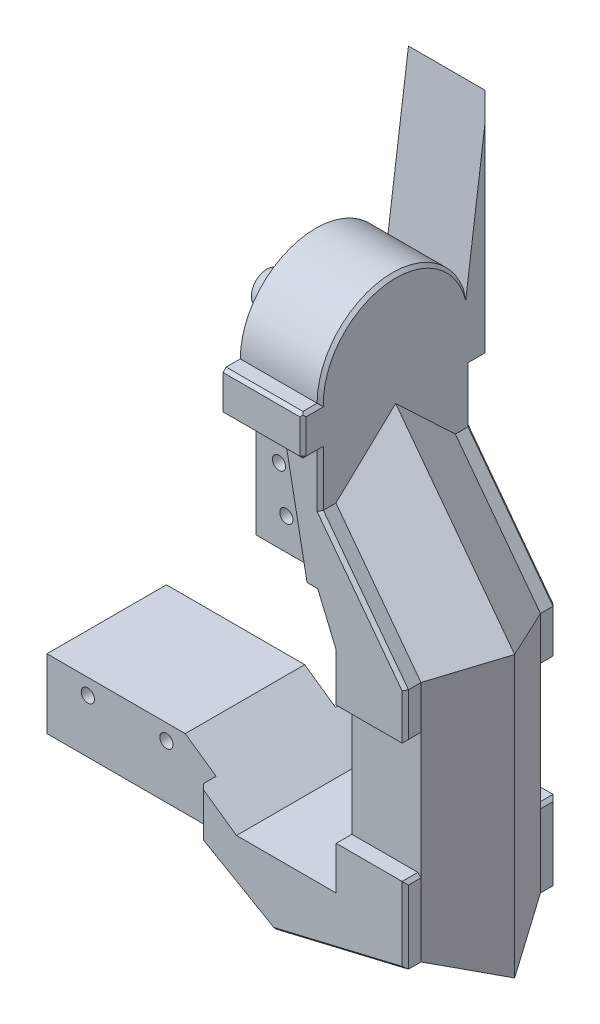
SolidWorks part; units mm, degrees
ref_plane "前视基准面" through (0, 0, 0) normal (0, 0, 1) x (1, 0, 0)
ref_plane "上视基准面" through (0, 0, 0) normal (0, 1, 0) x (1, 0, 0)
ref_plane "右视基准面" through (0, 0, 0) normal (1, 0, 0) x (0, 0, -1)
other "Configuration Table"
sketch "草图1" plane through (0, 0, 0) normal (0, 0, 1) x (1, 0, 0)
  line L0 (0, 0) -> (53.8, 0)
  line L1 (53.8, 0) -> (77, -13.3945)
  line L2 (77, -13.3945) -> (119, -3.4144)
  line L3 (119, -3.4144) -> (119, 73.5856)
  line L4 (119, 73.5856) -> (91.9365, 109.5)
  line L5 (91.9365, 109.5) -> (91.9365, 158)
  line L6 (91.9365, 158) -> (66.5044, 158)
  line L7 (66.5044, 158) -> (66.5044, 88)
  line L8 (66.5044, 88) -> (91.1544, 88)
  line L9 (91.1544, 88) -> (97, 74.0856)
  line L12 (65.3, 7.0856) -> (44, 22)
  line L13 (44, 22) -> (0, 22)
  line L14 (0, 22) -> (0, 0)
  line L15 (65.3, 7.0856) -> (97, 7.0856)
  line L16 (97, 7.0856) -> (97, 74.0856)
  circle A0 centre (73.8244, 111.53) radius 2.1
  circle A1 centre (76.1544, 98.03) radius 2.1
  circle A2 centre (13, 17) radius 2.1
  circle A3 centre (38, 17) radius 2.1
  dimension "D21" = 4.2
  dimension "D24" = 4.2
  dimension "D29" = 4.2
  dimension "D30" = 4.2
  dimension "D1" = 44
  dimension "D2" = 53
  dimension "D3" = 22
  dimension "D4" = 145
  dimension "D5" = 150
  dimension "D6" = 31.7
  dimension "D7" = 22
  dimension "D8" = 23.2
  dimension "D9" = 42
  dimension "D10" = 10.5
  dimension "D11" = 24.65
  dimension "D12" = 66
  dimension "D13" = 67.212
  dimension "D14" = 77
  dimension "D15" = 67
  dimension "D16" = 70
  dimension "D17" = 48.5
  dimension "D18" = 143
  dimension "D19" = 7.32
  dimension "D20" = 23.53
  dimension "D22" = 9.65
  dimension "D23" = 10.03
  dimension "D25" = 13
  dimension "D26" = 38
  dimension "D27" = 17
  dimension "D28" = 17
extrude "凸台-拉伸1" add sketch "草图1" along normal blind 38
sketch "草图2" plane through (91.9365, 0, 0) normal (1, 0, 0) x (0, 0, -1)
  line L0 (-38, 109.5) -> (-38, 158) construction
  line L1 (-38, 158) -> (0, 158) construction
  line L2 (0, 109.5) -> (0, 158) construction
  line L3 (-19, 109.5) -> (-19, 164.3174) construction
  line L5 (-38, 139) -> (-38, 158)
  line L6 (-38, 158) -> (0, 158)
  line L7 (0, 158) -> (0, 139)
  arc A0 (-38, 139) -> (0, 139) centre (-19, 139) cw
  circle A1 centre (-19, 139) radius 3
  line M6 (0, 109.5) -> (0, 158)
  line M7 (0, 158) -> (-38, 158)
  line M8 (-38, 158) -> (-38, 109.5)
  dimension "D1" = 6
extrude "切除-拉伸1" cut sketch "草图2" against normal through all contours A0 L6 M8 | A0 M7 M6
sketch "草图3" plane through (66.5044, 0, 0) normal (-1, 0, 0) x (0, 0, 1)
  line L3 (0, 139) -> (0, 88)
  line L4 (0, 88) -> (38, 88)
  line L5 (38, 88) -> (38, 139)
  line L6 (0, 139) -> (0, 88)
  line L7 (0, 88) -> (38, 88)
  line L8 (38, 88) -> (38, 139)
  circle A0 centre (19, 139) radius 3.15
  arc A1 (38, 139) -> (0, 139) centre (19, 139) ccw
  arc A2 (38, 139) -> (0, 139) centre (19, 139) ccw
  dimension "D2" = 6.3
  dimension "D1" = 0
extrude "切除-拉伸3" cut sketch "草图3" against normal blind 1 contours A0
ref_plane "基准面1" through (77, 0, 0) normal (-1, 0, 0) x (0, 0, 1)
sketch "草图4" plane through (77, 0, 0) normal (-1, 0, 0) x (0, 0, 1)
  line L0 (38, -13.3945) -> (0, -13.3945) construction
  line L1 (38, -13.3945) -> (0, -13.3945)
  line L2 (0, -13.3945) -> (19, -24.4851)
  line L3 (19, -24.4851) -> (38, -13.3945)
  dimension "D1" = 22
ref_plane "基准面2" through (0, 109.5, 0) normal (0, -1, 0) x (-1, 0, 0)
sketch "草图9" plane through (0, 109.5, 0) normal (0, -1, 0) x (-1, 0, 0)
  line L0 (-91.9365, -38) -> (-91.9365, 0) construction
  line L1 (-91.9365, -38) -> (-91.9365, 0)
sketch "草图10" plane through (0, 109.5, 0) normal (0, -1, 0) x (-1, 0, 0)
  line L0 (-91.9365, 0) -> (-103.0271, -19)
  line L1 (-103.0271, -19) -> (-91.9365, -38)
  line L2 (-91.9365, 0) -> (-91.9365, -38)
  dimension "D1" = 22
ref_plane "基准面3" through (0, 0, 19) normal (0, 0, 1) x (1, 0, 0)
sketch "草图13" plane through (0, 0, 19) normal (0, 0, 1) x (1, 0, 0)
  line L3 (77, -13.3945) -> (119, -3.4144) construction
  line L10 (91.9365, 127.4291) -> (129.79, 77.1959)
  line L11 (129.79, 77.1959) -> (129.79, -11.941)
  line L12 (129.79, -11.941) -> (77, -24.4851)
  line L13 (119, 73.5856) -> (91.9365, 109.5) construction
  line L14 (91.9365, 109.5) -> (91.9365, 139) construction
  line L15 (119, 73.5856) -> (91.9365, 109.5)
  line L16 (91.9365, 109.5) -> (91.9365, 139)
  line L17 (77, -13.3945) -> (77, -24.4851) construction
  line L18 (119, -3.4144) -> (119, 73.5856) construction
  dimension "D1" = 10.79
  dimension "D2" = 10.79
  dimension "D3" = 10.7901
sweep "扫描3" add profiles "草图4" path "草图13"
sketch "草图14" plane through (0, 0, 38) normal (0, 0, 1) x (1, 0, 0)
  line L0 (66.5044, 126.1486) -> (80.4341, 126.1486)
  line L1 (80.4341, 126.1486) -> (87.7424, 88)
  line L2 (97, 58.8709) -> (118.9999, 58.8709)
  line L3 (97, 20.7689) -> (118.9999, 20.7689)
  line L4 (53.8, 0) -> (53.8, 15.138)
  line L15 (91.9365, 109.4998) -> (91.9365, 139)
  line L16 (91.9365, 139) -> (66.5044, 139)
  line L17 (66.5044, 139) -> (66.5044, 88)
  line L18 (66.5044, 88) -> (91.1544, 88)
  line L19 (91.1544, 88) -> (97, 74.0856)
  line L20 (97, 74.0856) -> (97, 7.0856)
  line L21 (97, 7.0856) -> (65.3, 7.0856)
  line L22 (65.3, 7.0856) -> (44, 22)
  line L23 (44, 22) -> (0, 22)
  line L24 (0, 22) -> (0, 0)
  line L25 (0, 0) -> (53.8, 0)
  line L26 (53.8, 0) -> (77, -13.3945)
  line L27 (77, -13.3945) -> (118.9999, -3.4144)
  line L28 (118.9999, -3.4144) -> (118.9999, 73.5855)
  line L29 (118.9999, 73.5855) -> (91.9365, 109.4998)
  line L30 (91.9365, 109.4998) -> (91.9365, 139)
  line L31 (91.9365, 139) -> (66.5044, 139)
  line L32 (66.5044, 139) -> (66.5044, 88)
  line L33 (66.5044, 88) -> (91.1544, 88)
  line L34 (91.1544, 88) -> (97, 74.0856)
  line L35 (97, 74.0856) -> (97, 7.0856)
  line L36 (97, 7.0856) -> (65.3, 7.0856)
  line L37 (65.3, 7.0856) -> (44, 22)
  line L38 (44, 22) -> (0, 22)
  line L39 (0, 22) -> (0, 0)
  line L40 (0, 0) -> (53.8, 0)
  line L41 (53.8, 0) -> (77, -13.3945)
  line L42 (77, -13.3945) -> (118.9999, -3.4144)
  line L43 (118.9999, -3.4144) -> (118.9999, 73.5855)
  line L44 (118.9999, 73.5855) -> (91.9365, 109.4998)
  dimension "D1" = 0
extrude "凸台-拉伸2" add sketch "草图14" along normal blind 5
sketch "草图15" plane through (0, 0, 0) normal (0, 0, -1) x (-1, 0, 0)
  line L0 (-53.8, 0) -> (-53.8, 15.138) construction
  line L1 (-97, 20.7689) -> (-118.9999, 20.7689) construction
  line L2 (-97, 58.8709) -> (-118.9999, 58.8709) construction
  line L3 (-80.4341, 126.1486) -> (-87.7424, 88) construction
  line L4 (-66.5044, 126.1486) -> (-80.4341, 126.1486) construction
  line L5 (-53.8, 0) -> (-53.8, 15.138)
  line L6 (-97, 20.7689) -> (-118.9999, 20.7689)
  line L7 (-97, 58.8709) -> (-118.9999, 58.8709)
  line L8 (-80.4341, 126.1486) -> (-87.7424, 88)
  line L9 (-66.5044, 126.1486) -> (-80.4341, 126.1486)
  line L15 (-91.9365, 139) -> (-91.9365, 109.4998)
  line L16 (-91.9365, 109.4998) -> (-118.9999, 73.5855)
  line L17 (-118.9999, 73.5855) -> (-118.9999, -3.4144)
  line L18 (-118.9999, -3.4144) -> (-77, -13.3945)
  line L19 (-77, -13.3945) -> (-53.8, 0)
  line L20 (-53.8, 0) -> (0, 0)
  line L21 (0, 0) -> (0, 22)
  line L22 (0, 22) -> (-44, 22)
  line L23 (-44, 22) -> (-65.3, 7.0856)
  line L24 (-65.3, 7.0856) -> (-97, 7.0856)
  line L25 (-97, 7.0856) -> (-97, 74.0856)
  line L26 (-97, 74.0856) -> (-91.1544, 88)
  line L27 (-91.1544, 88) -> (-66.5044, 88)
  line L28 (-66.5044, 88) -> (-66.5044, 139)
  line L29 (-66.5044, 139) -> (-91.9365, 139)
  line L30 (-91.9365, 139) -> (-91.9365, 109.4998)
  line L31 (-91.9365, 109.4998) -> (-118.9999, 73.5855)
  line L32 (-118.9999, 73.5855) -> (-118.9999, -3.4144)
  line L33 (-118.9999, -3.4144) -> (-77, -13.3945)
  line L34 (-77, -13.3945) -> (-53.8, 0)
  line L35 (-53.8, 0) -> (0, 0)
  line L36 (0, 0) -> (0, 22)
  line L37 (0, 22) -> (-44, 22)
  line L38 (-44, 22) -> (-65.3, 7.0856)
  line L39 (-65.3, 7.0856) -> (-97, 7.0856)
  line L40 (-97, 7.0856) -> (-97, 74.0856)
  line L41 (-97, 74.0856) -> (-91.1544, 88)
  line L42 (-91.1544, 88) -> (-66.5044, 88)
  line L43 (-66.5044, 88) -> (-66.5044, 139)
  line L44 (-66.5044, 139) -> (-91.9365, 139)
  line M16 (-91.9365, 139) -> (-91.9365, 109.4998)
  line M17 (-91.9365, 109.4998) -> (-118.9999, 73.5855)
  line M18 (-118.9999, 73.5855) -> (-118.9999, -3.4144)
  line M19 (-118.9999, -3.4144) -> (-77, -13.3945)
  line M20 (-77, -13.3945) -> (-53.8, 0)
  line M24 (-44, 22) -> (-65.3, 7.0856)
  line M25 (-65.3, 7.0856) -> (-97, 7.0856)
  line M26 (-97, 7.0856) -> (-97, 74.0856)
  line M27 (-97, 74.0856) -> (-91.1544, 88)
  line M28 (-91.1544, 88) -> (-66.5044, 88)
  line M29 (-66.5044, 88) -> (-66.5044, 139)
  line M30 (-66.5044, 139) -> (-91.9365, 139)
  dimension "D1" = 0
extrude "凸台-拉伸3" add sketch "草图15" along normal blind 5 contours L9 L7 L8 M29 M30 M16 M17 M18 M26 M27 M28 | L6 L5 M26 M18 M19 M20 M24 M25
sketch "草图16" plane through (91.9365, 0, 0) normal (1, 0, 0) x (0, 0, -1)
  line L0 (-43, 109.4998) -> (-43, 139) construction
  arc A0 (-43, 139) -> (5, 139) centre (-19, 139) cw
extrude "拉伸-薄壁2" add sketch "草图16" along direction (1, 0, 0) on the side against the normal up to surface (25.4322 mm away) thin
sketch "草图17" plane through (91.9365, 0, 0) normal (1, 0, 0) x (0, 0, -1)
  line L0 (5, 128.4582) -> (10.5, 128.4582)
  line L3 (10.5, 128.4582) -> (10.5, 198.4582)
  line L4 (10.5, 198.4582) -> (3.6023, 147.0707)
  line L6 (-43, 139) -> (-43, 109.4998)
  line L7 (-43, 109.4998) -> (-38, 109.4998)
  line L8 (-38, 109.4998) -> (-19, 127.4291)
  line L9 (-19, 127.4291) -> (0, 109.4998)
  line L10 (0, 109.4998) -> (5, 109.4998)
  line L11 (5, 109.4998) -> (5, 139)
  line L12 (-43, 139) -> (-43, 109.4998)
  line L13 (-43, 109.4998) -> (-38, 109.4998)
  line L14 (-38, 109.4998) -> (-19, 127.4291)
  line L15 (-19, 127.4291) -> (0, 109.4998)
  line L16 (0, 109.4998) -> (5, 109.4998)
  line L17 (5, 109.4998) -> (5, 139)
  arc A1 (5, 139) -> (-43, 139) centre (-19, 139) ccw
  arc A2 (5, 139) -> (-43, 139) centre (-19, 139) ccw
  arc M10 (5, 139) -> (-43, 139) centre (-19, 139) ccw
  line M16 (5, 109.4998) -> (5, 139)
  dimension "D2" = 5.5
  dimension "D3" = 70
  dimension "D1" = 0
extrude "凸台-拉伸7" add sketch "草图17" against normal up to surface (25.4322 mm away) contours L3 L4 L0 M10 M16 up to face at (66.5044, 122.8243, 19)
sketch "草图18" plane through (0, 128.4582, 0) normal (0, -1, 0) x (1, 0, 0)
  line L4 (66.5044, -5) -> (66.5044, -10.5)
  line L5 (66.5044, -10.5) -> (91.9365, -10.5)
  line L6 (91.9365, -10.5) -> (91.9365, -5)
  line L7 (91.9365, -5) -> (66.5044, -5)
  line L8 (66.5044, -5) -> (66.5044, -10.5)
  line L9 (66.5044, -10.5) -> (91.9365, -10.5)
  line L10 (91.9365, -10.5) -> (91.9365, -5)
  line L11 (91.9365, -5) -> (66.5044, -5)
  dimension "D1" = 0
extrude "凸台-拉伸8" add sketch "草图18" along normal up to surface (2.3096 mm away) up to face at (73.4692, 126.1486, -2.5)
sketch "草图19" plane through (0, 0, 43) normal (0, 0, 1) x (1, 0, 0)
  line L0 (80.4341, 126.1486) -> (91.9365, 126.1486)
  line L11 (97, 74.0856) -> (97, 58.8709)
  line L12 (97, 58.8709) -> (118.9999, 58.8709)
  line L13 (118.9999, 58.8709) -> (118.9999, 73.5855)
  line L14 (118.9999, 73.5855) -> (91.9365, 109.4998)
  line L15 (91.9365, 109.4998) -> (91.9365, 139)
  line L16 (91.9365, 139) -> (66.5044, 139)
  line L17 (66.5044, 139) -> (66.5044, 126.1486)
  line L18 (66.5044, 126.1486) -> (80.4341, 126.1486)
  line L19 (80.4341, 126.1486) -> (87.7424, 88)
  line L20 (87.7424, 88) -> (91.1544, 88)
  line L21 (91.1544, 88) -> (97, 74.0856)
  line L26 (91.9365, 126.1486) -> (91.9365, 139)
  line L27 (91.9365, 139) -> (66.5044, 139)
  line L28 (66.5044, 139) -> (66.5044, 126.1486)
  line L29 (66.5044, 126.1486) -> (80.4341, 126.1486)
  line L31 (87.7424, 88) -> (91.1544, 88)
  line M16 (91.9365, 109.4998) -> (91.9365, 139)
  line M17 (91.9365, 139) -> (66.5044, 139)
  line M18 (66.5044, 139) -> (66.5044, 126.1486)
  line M19 (66.5044, 126.1486) -> (80.4341, 126.1486)
  dimension "D1" = 0
extrude "凸台-拉伸10" add sketch "草图19" along normal blind 5.5 contours L0 M19 M16 M17 M18
sketch "草图20" plane through (66.5044, 0, 0) normal (-1, 0, 0) x (0, 0, 1)
  line L9 (-10.5, 198.4582) -> (-10.5, 126.1486)
  line L10 (-10.5, 126.1486) -> (0, 126.1486)
  line L11 (0, 126.1486) -> (0, 88)
  line L12 (0, 88) -> (38, 88)
  line L13 (38, 88) -> (38, 126.1486)
  line L14 (38, 126.1486) -> (48.5, 126.1486)
  line L15 (48.5, 126.1486) -> (48.5, 139)
  line L16 (48.5, 139) -> (43, 139)
  line L17 (-3.6023, 147.0707) -> (-10.5, 198.4582)
  line L18 (-10.5, 198.4582) -> (-10.5, 126.1486)
  line L19 (-10.5, 126.1486) -> (0, 126.1486)
  line L20 (0, 126.1486) -> (0, 88)
  line L21 (0, 88) -> (38, 88)
  line L22 (38, 88) -> (38, 126.1486)
  line L23 (38, 126.1486) -> (48.5, 126.1486)
  line L24 (48.5, 126.1486) -> (48.5, 139)
  line L25 (48.5, 139) -> (43, 139)
  line L26 (-3.6023, 147.0707) -> (-10.5, 198.4582)
  circle A0 centre (19, 139) radius 3.15 construction
  arc A1 (43, 139) -> (-3.6023, 147.0707) centre (19, 139) ccw
  arc A2 (43, 139) -> (-3.6023, 147.0707) centre (19, 139) ccw
  circle A3 centre (19, 139) radius 3.15
  circle A4 centre (19, 139) radius 11.5
  dimension "D2" = 23
  dimension "D1" = 0
ref_plane "基准面4" through (51.0044, 0, 0) normal (-1, 0, 0) x (0, 0, 1)
sketch "草图21" plane through (51.0044, 0, 0) normal (-1, 0, 0) x (0, 0, 1)
  circle A0 centre (19, 139) radius 11.5 construction
  circle A1 centre (19, 139) radius 3.15 construction
  circle A2 centre (19, 139) radius 11.5
  circle A3 centre (19, 139) radius 3.15
  circle A4 centre (19, 139) radius 5
  dimension "D1" = 10
loft "放样1" add section "草图21" section "草图20"
sketch "草图23" plane through (51.0044, 0, 0) normal (-1, 0, 0) x (0, 0, 1)
  circle A0 centre (19, 139) radius 3.15
  circle A1 centre (19, 139) radius 5
  circle A2 centre (19, 139) radius 5
  dimension "D2" = 6.3
  dimension "D1" = 0
extrude "切除-拉伸4" cut sketch "草图23" against normal blind 15.5 contours A0
chamfer "倒角1" distance 1 angle 45 1 edges at (79.2205, 139, 48.5)
chamfer "倒角3" distance 1 angle 45 26 edges at (53.8, 7.569, 43) (118.9999, 20.7689, 40.5) (65.4, -6.6973, 43) (98, -8.4045, 43) (118.9999, 8.6772, 43) (118.9999, 58.8709, 40.5) (118.9999, 66.2282, 43) (105.4682, 91.5427, 43) (91.9365, 117.8242, 43) (118.9999, 58.8709, -2.5) (105.4682, 91.5427, -5) (118.9999, 66.2282, -5) (118.9999, 20.7689, -2.5) (118.9999, 8.6772, -5) (98, -8.4045, -5) (65.4, -6.6973, -5) (53.8, 7.569, -5) (91.9365, 162.648, 23.0954) (91.9365, 162.3034, -10.5) (91.9365, 117.8242, -5) (91.9365, 126.1486, -7.75) (91.9365, 126.1486, 45.75) (79.2205, 126.1486, 48.5) (91.9365, 132.0743, 48.5) (91.9365, 139, 45.25) (91.9365, 138.5, 48)
